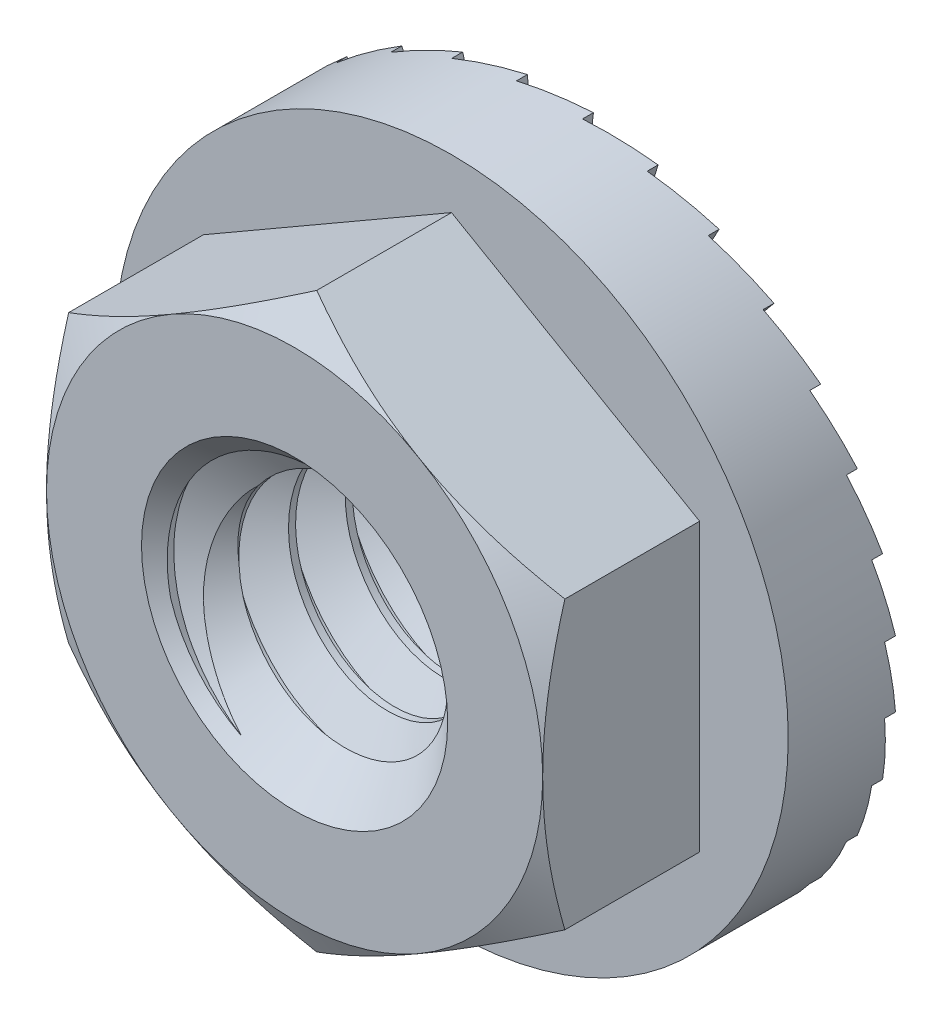
SolidWorks part; units mm, degrees
ref_plane "Front Plane" through (0, 0, 0) normal (0, 0, 1) x (1, 0, 0)
ref_plane "Top Plane" through (0, 0, 0) normal (0, 1, 0) x (1, 0, 0)
ref_plane "Right Plane" through (0, 0, 0) normal (1, 0, 0) x (0, 0, -1)
sketch "Sketch1" plane through (0, 0, 0) normal (0, 0, 1) x (1, 0, 0)
  line L1 (0, 6.4158) -> (-5.5563, 3.2079)
  line L2 (-5.5563, 3.2079) -> (-5.5563, -3.2079)
  line L3 (-5.5563, -3.2079) -> (0, -6.4158)
  line L4 (0, -6.4158) -> (5.5562, -3.2079)
  line L5 (5.5562, -3.2079) -> (5.5562, 3.2079)
  line L6 (5.5562, 3.2079) -> (0, 6.4158)
  circle A0 centre (0, 0) radius 5.5563 construction
  dimension "Hex" = 11.1125
extrude "Extrude1" add sketch "Sketch1" against normal blind 5.9531
sketch "Sketch13" plane through (0, 0, -5.9531) normal (0, 0, -1) x (-1, 0, 0)
  circle A0 centre (0, 0) radius 7.5406
  dimension "Flange od" = 15.0812
extrude "Extrude3" add sketch "Sketch13" against normal blind 2.4384
sketch "Sketch2" plane through (0, 0, 0) normal (0, 0, 1) x (1, 0, 0)
  circle A0 centre (0, 0) radius 5.5563 construction
  circle A1 centre (0, 0) radius 5.5563
extrude "Cut-Extrude1" cut sketch "Sketch2" against normal through all draft 60 flip side to cut
sketch "Sketch4" plane through (0, 0, 0) normal (0, 0, 1) x (1, 0, 0)
  circle A0 centre (0, 0) radius 3.175
  dimension "Thread Dia" = 6.35
extrude "Cut-Extrude3" cut sketch "Sketch4" against normal through all
sketch "Sketch7" plane through (0, 0, 0) normal (0, 0, 1) x (1, 0, 0)
  circle A4 centre (0, 0) radius 3.429
  circle A5 centre (0, 0) radius 3.429
  dimension "D1" = 0.254
sketch "Sketch8" plane through (0, 0, -5.9531) normal (0, 0, -1) x (-1, 0, 0)
  circle A1 centre (0, 0) radius 3.429
  circle A2 centre (0, 0) radius 3.429 construction
sketch "Sketch5" plane through (0, 0, 0) normal (0, 0, 1) x (1, 0, 0)
  circle A0 centre (0, 0) radius 3.175 construction
  circle A1 centre (0, 0) radius 3.175
curve "Helix/Spiral1" pitch 1.27 height 7.2231 turns 5.6875 parameters "pitch"=1.27
sketch "Sketch9" plane through (0, 0, 0) normal (1, 0, 0) x (0, 0, -1)
  line L0 (-0.635, 3.175) -> (-0.4762, 3.175)
  line L1 (-0.4762, 3.175) -> (0, 2.3501)
  line L2 (-0.635, 3.175) -> (-1.1112, 2.3501)
  line L3 (-1.1112, 2.3501) -> (0, 2.3501)
  line L4 (-0.5556, 3.175) -> (-0.5556, 2.3501) construction
  line L5 (-0.8731, 2.7626) -> (-0.2381, 2.7626) construction
  line L7 (0, 2.3501) -> (0, 3.175) construction
  line L8 (0, 3.175) -> (0, -3.175) construction
  dimension "D1" = 0.1588
  dimension "D2" = 0.635
  dimension "D3" = 60
sketch "Sketch12" plane through (0, 0, 0) normal (0, 0, 1) x (1, 0, 0)
  circle A0 centre (0, 0) radius 2.3501
  circle A1 centre (0, 0) radius 3.175 construction
  circle A2 centre (0, 0) radius 3.175
extrude "Extrude2" add sketch "Sketch12" against normal up to surface (5.9531 mm away)
sweep "Cut-Sweep1" cut profiles "Sketch9" path "Helix/Spiral1"
extrude "Cut-Extrude6" cut sketch "Sketch7" against normal through all draft 45
extrude "Cut-Extrude7" cut sketch "Sketch8" against normal through all draft 45
sketch "Sketch14" plane through (0, 0, -5.9531) normal (0, 0, -1) x (-1, 0, 0)
  circle A4 centre (0, 0) radius 5.461
  circle A5 centre (0, 0) radius 5.461
  dimension "D1" = 2.032
extrude "Cut-Extrude8" cut sketch "Sketch14" against normal blind 0.2438 flip side to cut
sketch "Sketch15" plane through (0, 0, -5.7093) normal (0, 0, -1) x (-1, 0, 0)
  line L0 (-0.5353, 5.4347) -> (-0.7391, 7.5043)
  line L1 (0.5353, 5.4347) -> (0.7391, 7.5043)
  line L2 (0, 0) -> (0.5353, 5.4347) construction
  line L3 (0, 0) -> (-0.5353, 5.4347) construction
  circle A0 centre (0, 0) radius 7.5406 construction
  circle A1 centre (0, 0) radius 5.461 construction
  arc A2 (0.7391, 7.5043) -> (-0.7391, 7.5043) centre (0, 0) ccw
  arc A3 (0.5353, 5.4347) -> (-0.5353, 5.4347) centre (0, 0) ccw
  dimension "D1" = 11.25
extrude "Extrude4" add sketch "Sketch15" along normal up to surface (0.2438 mm away) separate body up to face at (-3.429, 0, -5.9531)
sketch "Sketch16" plane through (0, 0, 0) normal (0, 1, 0) x (1, 0, 0)
  line L0 (-0.7391, 5.7093) -> (0.7391, 5.9531)
  line L4 (-0.7391, 5.7093) -> (0.7391, 5.7093)
  line L5 (0.7391, 5.7093) -> (0.7391, 5.9531)
  line L6 (0.7391, 5.9531) -> (-0.7391, 5.9531)
  line L7 (-0.7391, 5.9531) -> (-0.7391, 5.7093)
  line L8 (-0.7391, 5.7093) -> (0.7391, 5.7093) construction
  line L9 (0.7391, 5.7093) -> (0.7391, 5.9531) construction
  line L10 (0.7391, 5.9531) -> (-0.7391, 5.9531)
  line L11 (-0.7391, 5.9531) -> (-0.7391, 5.7093)
  dimension "D1" = 0
extrude "Cut-Extrude9" cut sketch "Sketch16" along normal through all
pattern_circular "CirPattern1" count 32 over 360 about axis through (0, 0, 0) along (0, 0, 1) of bodies 119
combine bodies "Combine1" operation type add bodies to combine 117 119 120 121 122 123 124 125 126 127 128 129 130 131 132 133 134 135 136 137 139 140 141 142 143 144 145 146 147 148 149 150 151
sketch "Sketch17" plane through (0, 0, 0) normal (1, 0, 0) x (0, 0, -1)
  line L0 (5.9531, 7.5406) -> (5.9531, -7.5406) construction
  line L1 (3.5147, 7.5406) -> (3.5147, -7.5406) construction
  dimension "D1" = 2.4384
sketch "Sketch18" plane through (0, 0, -3.5147) normal (0, 0, 1) x (1, 0, 0)
  circle A0 centre (0, 0) radius 7.5406
  circle A1 centre (0, 0) radius 7.5406 construction
equation "\"D2@Sketch9\" = \"pitch@Helix/Spiral1\"*.5"
equation "\"D3@Helix/Spiral1\" = \"pitch@Helix/Spiral1\"+\"Height@Extrude1\""
equation "\"D1@Sketch9\" = \"pitch@Helix/Spiral1\"*.125"
equation "\"D1@Cut-Extrude8\" = \"flange thickness@Extrude3\"*.1"
equation "\"D1@Sketch17\" = \"flange thickness@Extrude3\""
